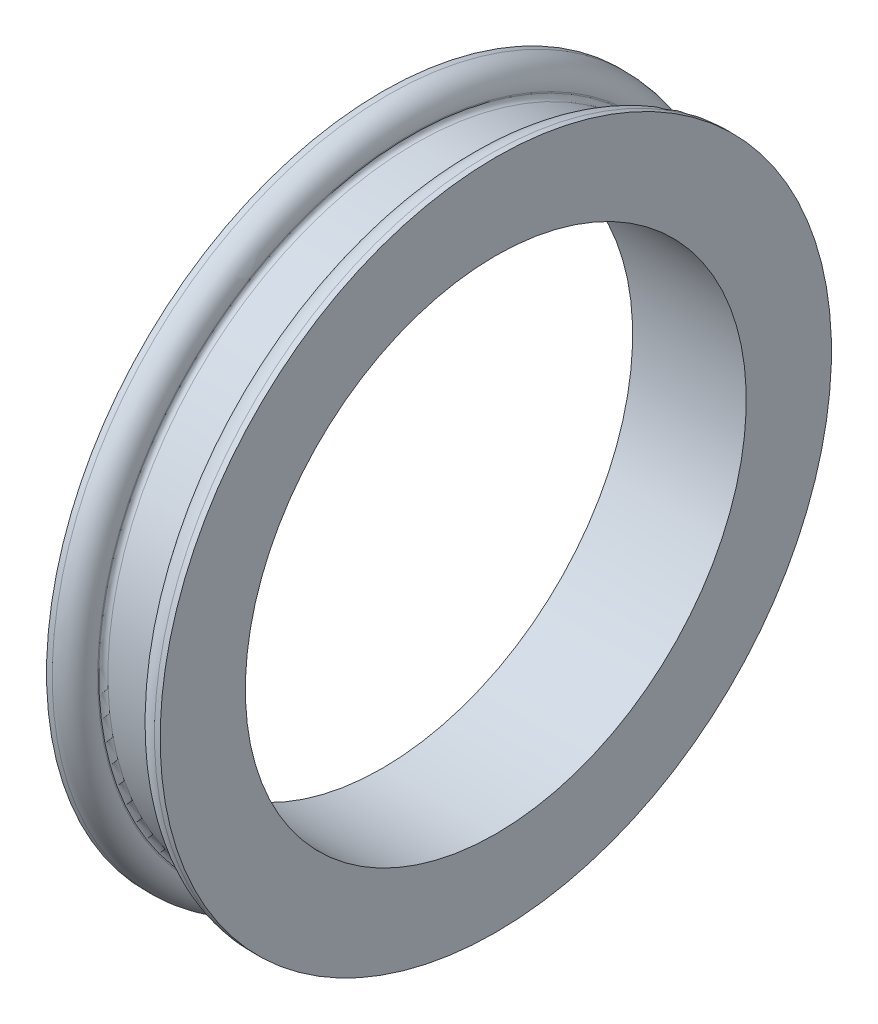
SolidWorks part; units mm, degrees
material "Nylon 101"
ref_plane "Front Plane" through (0, 0, 0) normal (0, 0, 1) x (1, 0, 0)
ref_plane "Top Plane" through (0, 0, 0) normal (0, 1, 0) x (1, 0, 0)
ref_plane "Right Plane" through (0, 0, 0) normal (1, 0, 0) x (0, 0, -1)
sketch "Sketch1" plane through (0, 0, 0) normal (0, 0, 1) x (1, 0, 0)
  line L0 (-11.2276, 0) -> (11.2276, 0) construction
  line L1 (0, 0) -> (0, 14) construction
  line L2 (-3.175, 14) -> (3.175, 14)
  line L3 (-3.175, 14) -> (-3.175, 18.7625)
  line L4 (0, 14) -> (0, 17.175) construction
  line L5 (-1.3335, 17.175) -> (1.3335, 17.175)
  line L6 (3.175, 14) -> (3.175, 18.7625)
  line L7 (-1.5875, 17.429) -> (-1.5875, 17.4925)
  line L8 (-2.8575, 18.7625) -> (-3.175, 18.7625)
  line L9 (1.5875, 17.429) -> (1.5875, 17.4925)
  line L10 (2.8575, 18.7625) -> (3.175, 18.7625)
  arc A0 (-1.5875, 17.4925) -> (-2.8575, 18.7625) centre (-2.8575, 17.4925) ccw
  arc A1 (2.8575, 18.7625) -> (1.5875, 17.4925) centre (2.8575, 17.4925) ccw
  arc A2 (-1.5875, 17.429) -> (-1.3335, 17.175) centre (-1.3335, 17.429) ccw
  arc A3 (1.3335, 17.175) -> (1.5875, 17.429) centre (1.3335, 17.429) ccw
  point P20 (-1.5875, 17.175)
  point P23 (1.5875, 17.175)
  dimension "D6" = 1.27
  dimension "D7" = 1.27
  dimension "D8" = 0.254
  dimension "D9" = 0.254
  dimension "D1" = 14
  dimension "D2" = 1.5875
  dimension "D3" = 4.7625
  dimension "D4" = 3.175
  dimension "D5" = 1.5875
  dimension "D10" = 1.5875
  dimension "D11" = 1.5875
revolve "Revolve1" add sketch "Sketch1" angle 360 about L0
